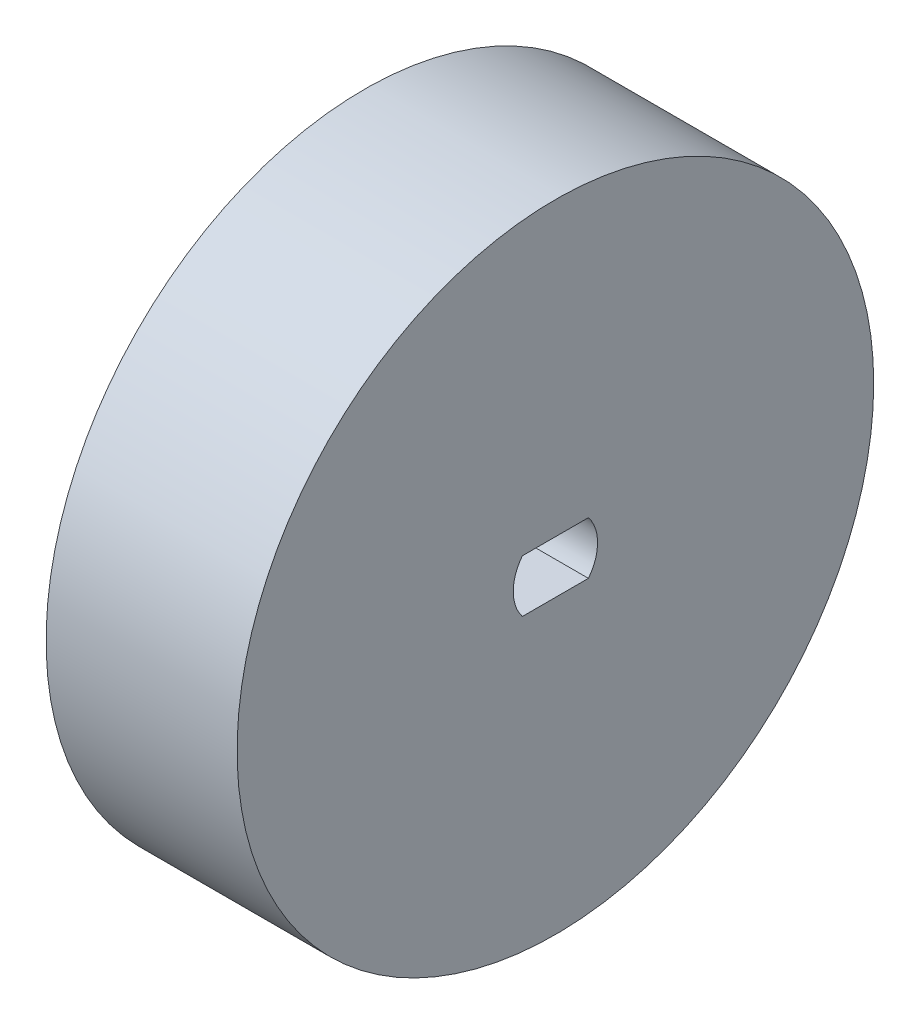
SolidWorks part; units mm, degrees
ref_plane "Front Plane" through (0, 0, 0) normal (0, 0, 1) x (1, 0, 0)
ref_plane "Top Plane" through (0, 0, 0) normal (0, 1, 0) x (1, 0, 0)
ref_plane "Right Plane" through (0, 0, 0) normal (1, 0, 0) x (0, 0, -1)
sketch "Sketch1" plane through (0, 0, 0) normal (1, 0, 0) x (0, 0, -1)
  line L0 (-2.0736, 1.65) -> (2.0736, 1.65)
  line L1 (-2.0736, -1.65) -> (2.0736, -1.65)
  circle A0 centre (0, 0) radius 20
  circle A1 centre (0, 0) radius 2.65
  point P8 (-2.0736, -1.65)
  dimension "D1" = 40
  dimension "D2" = 5.3
  dimension "D3" = 3.3
extrude "Boss-Extrude1" add sketch "Sketch1" against normal blind 12 contours A0 A1 | L0 A1 | L1 A1 region at (0, 2.0573, 0) region at (0, -2.0573, 0) region at (0, 0, 19.4343)
